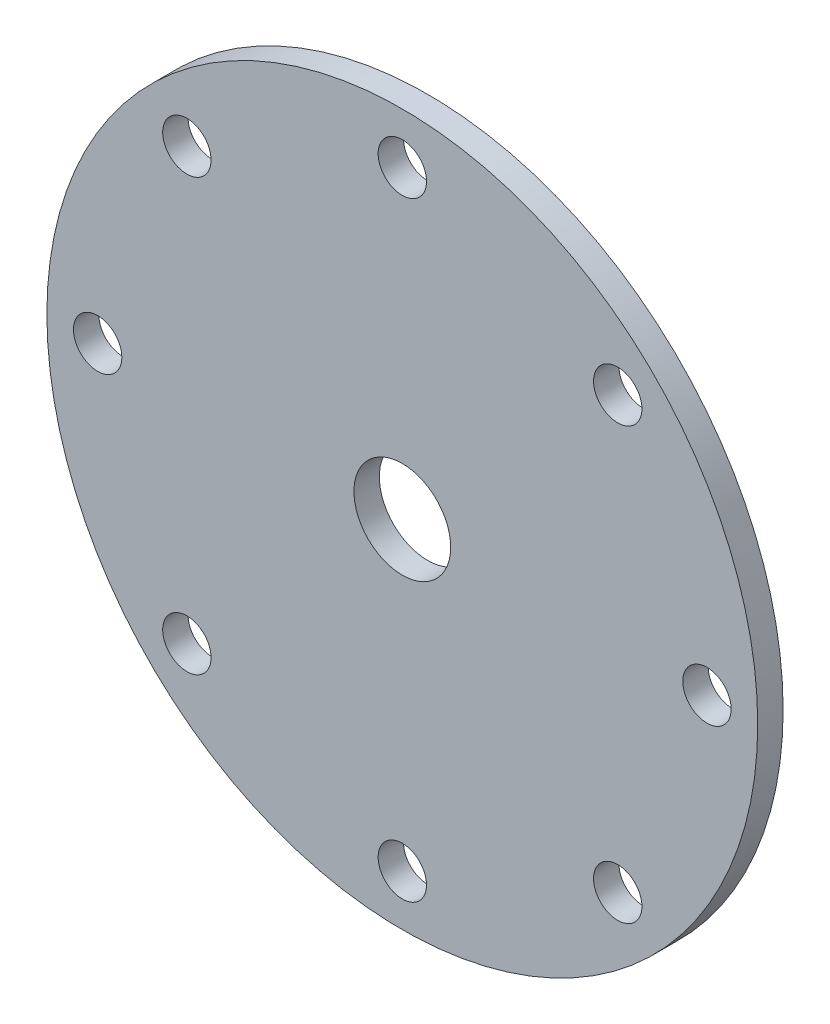
SolidWorks part; units mm, degrees
ref_plane "Front Plane" through (0, 0, 0) normal (0, 0, 1) x (1, 0, 0)
ref_plane "Top Plane" through (0, 0, 0) normal (0, 1, 0) x (1, 0, 0)
ref_plane "Right Plane" through (0, 0, 0) normal (1, 0, 0) x (0, 0, -1)
sketch "Sketch1" plane through (0, 0, 0) normal (0, 0, 1) x (1, 0, 0)
  line L0 (0, 70) -> (0, -70) construction
  line L1 (-70, 0) -> (70, 0) construction
  line L2 (-42.4264, 42.4264) -> (42.4264, -42.4264) construction
  line L3 (-42.4264, -42.4264) -> (42.4264, 42.4264) construction
  circle A0 centre (0, 0) radius 70
  circle A1 centre (0, 0) radius 9.525
  circle A2 centre (0, 60) radius 4.7625
  circle A6 centre (42.4264, 42.4264) radius 4.7625
  circle A7 centre (60, 0) radius 4.7625
  circle A8 centre (42.4264, -42.4264) radius 4.7625
  circle A9 centre (0, -60) radius 4.7625
  circle A10 centre (-42.4264, -42.4264) radius 4.7625
  circle A11 centre (-60, 0) radius 4.7625
  circle A12 centre (-42.4264, 42.4264) radius 4.7625
  dimension "D1" = 140
  dimension "D2" = 19.05
  dimension "D3" = 9.525
  dimension "D6" = 10
  dimension "D4" = 10
  dimension "D5" = 8
extrude "Rotor Disc" add sketch "Sketch1" along normal blind 5 contours A0 A12 A11 A10 A8 A7 A6 A1 A2 region at (-68.0201, 0, 0)
